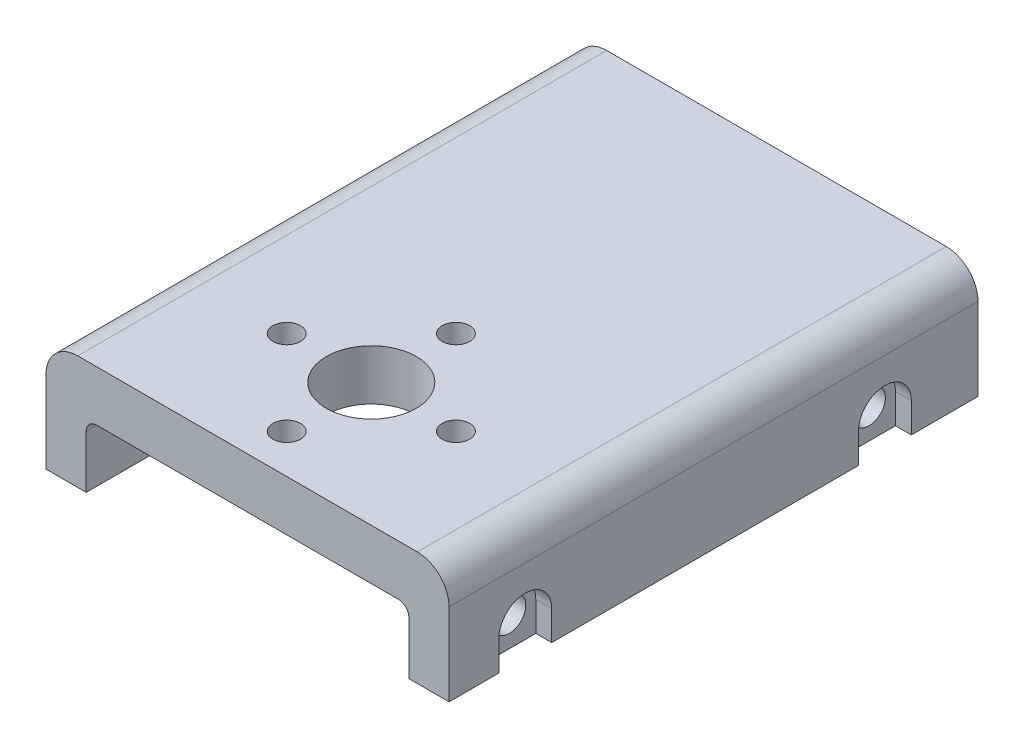
SolidWorks part; units mm, degrees
material "Onyx w/ CF"
ref_plane "Front Plane" through (0, 0, 0) normal (0, 0, 1) x (1, 0, 0)
ref_plane "Top Plane" through (0, 0, 0) normal (0, 1, 0) x (1, 0, 0)
ref_plane "Right Plane" through (0, 0, 0) normal (1, 0, 0) x (0, 0, -1)
sketch "Sketch1" plane through (0, 0, 0) normal (1, 0, 0) x (0, 0, -1)
  line L3 (-25, -10.775) -> (-25, 0)
  line L4 (-25, 0) -> (25, 0)
  line L5 (25, 0) -> (25, -10.775)
  line L6 (25, -10.775) -> (-25, -10.775)
  point P4 (0, 0)
  dimension "D1" = 10.775
  dimension "D2" = 50
extrude "Boss-Extrude1" add sketch "Sketch1" along normal mid plane 38.1
sketch "Sketch2" plane through (0, 0, 25) normal (0, 0, 1) x (1, 0, 0)
  line L0 (19.05, -10.775) -> (-19.05, -10.775) construction
  line L1 (-15.25, -10.775) -> (15.25, -10.775)
  line L2 (-15.25, -10.775) -> (-15.25, -4.775)
  line L3 (-15.25, -4.775) -> (15.25, -4.775)
  line L4 (15.25, -10.775) -> (15.25, -4.775)
  point P6 (0, -4.775)
  dimension "D1" = 30.5
  dimension "D2" = 6
extrude "Cut-Extrude1" cut sketch "Sketch2" against normal through all
sketch "Sketch3" plane through (0, -4.775, 0) normal (0, -1, 0) x (1, 0, 0)
  line L0 (15.25, 25) -> (-15.25, 25) construction
  circle A0 centre (0, 13.3) radius 4.25
  dimension "D2" = 8.5
  dimension "D1" = 11.7
extrude "Cut-Extrude2" cut sketch "Sketch3" against normal through all
hole_wizard "M2 Clearance Hole1" positions "Sketch4" profile "Sketch5" hole size "M2" standard "ANSI Metric" end condition through all
sketch "Sketch4" plane through (0, -4.775, 0) normal (0, -1, 0) x (-1, 0, 0)
  circle A0 centre (0, -13.3) radius 8
  circle A1 centre (0, -13.3) radius 4.25 construction
  point P0 (8, -13.3)
  point P2 (0, -21.3)
  point P4 (-8, -13.3)
  point P6 (0, -5.3)
  dimension "D1" = 16
sketch "Sketch5" plane through (-8, -4.775, 13.3) normal (1, 0, 0) x (0, 0, -1)
  line L0 (0, 0) -> (0, 4.775)
  line L1 (0, 4.775) -> (1.3, 4.775)
  line L2 (1.3, 4.775) -> (1.3, 0)
  line L5 (1.3, 0) -> (0, 0)
  line L11 (0, -6.35) -> (0, 107.95) construction
  dimension "Thru Hole Dia." = 2.6
  dimension "Thru Hole Depth" = 4.775
hole_wizard "M2.5 Clearance Hole1" positions "Sketch6" profile "Sketch7" hole size "M2.5" standard "ANSI Metric" end condition through all
sketch "Sketch6" plane through (-19.05, 0, 0) normal (-1, 0, 0) x (0, 0, 1)
  line L0 (-16.2, -7.975) -> (17.8, -7.975) construction
  line L2 (-25, -10.775) -> (25, -10.775) construction
  line L3 (-25, -4.775) -> (-25, -10.775) construction
  point P0 (-16.2, -7.975)
  point P2 (17.8, -7.975)
  dimension "D1" = 2.8
  dimension "D2" = 8.8
  dimension "D3" = 34
sketch "Sketch7" plane through (-19.05, -7.975, -16.2) normal (0, 1, 0) x (0, 0, 1)
  line L0 (0, 0) -> (0, 38.1)
  line L1 (0, 38.1) -> (1.55, 38.1)
  line L2 (1.55, 38.1) -> (1.55, 0)
  line L5 (1.55, 0) -> (0, 0)
  line L11 (0, -6.35) -> (0, 107.95) construction
  dimension "Thru Hole Dia." = 3.1
  dimension "Thru Hole Depth" = 38.1
sketch "Sketch8" plane through (19.05, 0, 0) normal (1, 0, 0) x (0, 0, -1)
  line L0 (-20.3, -7.975) -> (-20.3, -10.775)
  line L1 (-25, -10.775) -> (25, -10.775) construction
  line L2 (-20.3, -10.775) -> (-15.3, -10.775)
  line L3 (-15.3, -10.775) -> (-15.3, -7.975)
  line L4 (0, 0) -> (0, -8.775) construction
  line L5 (25, 0) -> (-25, 0) construction
  line L6 (13.7, -7.975) -> (13.7, -10.775)
  line L7 (13.7, -10.775) -> (18.7, -10.775)
  line L8 (18.7, -10.775) -> (18.7, -7.975)
  arc A0 (-15.3, -7.975) -> (-20.3, -7.975) centre (-17.8, -7.975) ccw
  circle A1 centre (-17.8, -7.975) radius 1.55 construction
  arc A2 (18.7, -7.975) -> (13.7, -7.975) centre (16.2, -7.975) ccw
  circle A3 centre (16.2, -7.975) radius 1.55 construction
  dimension "D2" = 5
extrude "Cut-Extrude3" cut sketch "Sketch8" against normal blind 1.5
extrude "Cut-Extrude4" cut sketch "Sketch8<2>" along normal blind 1.5 from surface starting at face at (-19.05, -7.975, -14.65)
sketch "Sketch8<2>" plane through (19.05, 0, 0) normal (1, 0, 0) x (0, 0, -1) same geometry as "Sketch8"
fillet "Fillet1" radius 1 2 edges at (-15.25, -4.775, 0) (15.25, -4.775, 0)
fillet "Fillet2" radius 3 2 edges at (-19.05, 0, 0) (19.05, 0, 0)
